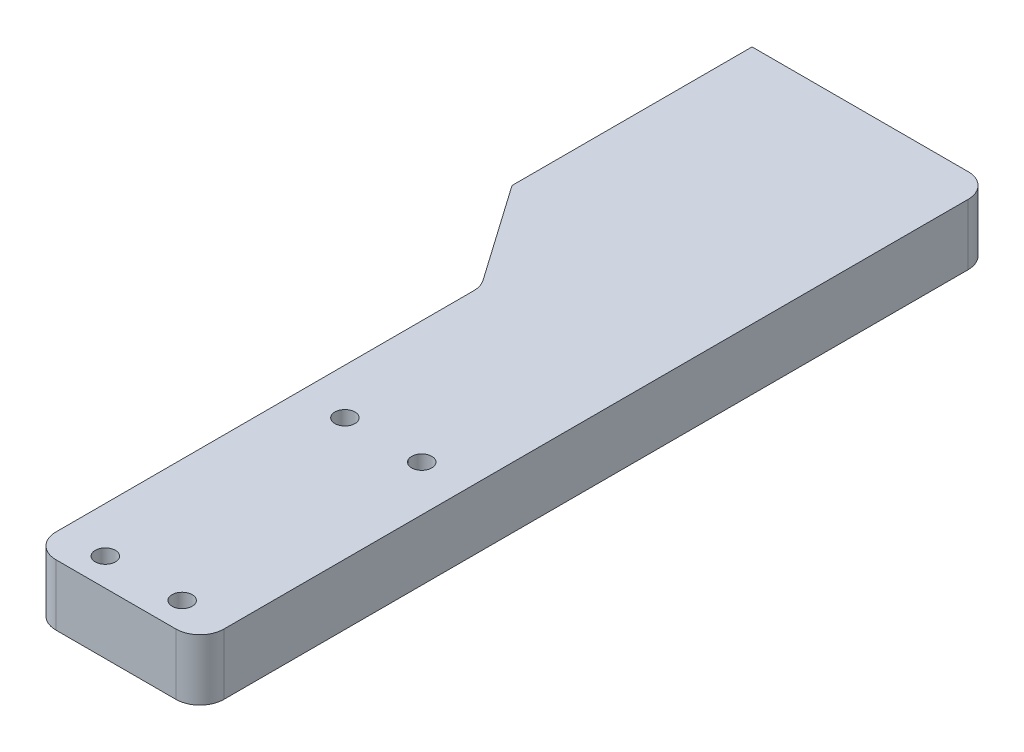
SolidWorks part; units mm, degrees
note: The reader was unsure of these and kept them because the rebuilt part matched: shared geometry of "Sketch26<3>".
ref_plane "Front Plane" through (0, 0, 0) normal (0, 0, 1) x (1, 0, 0)
ref_plane "Top Plane" through (0, 0, 0) normal (0, 1, 0) x (1, 0, 0)
ref_plane "Right Plane" through (0, 0, 0) normal (1, 0, 0) x (0, 0, -1)
sketch "Sketch12" plane through (0, 0, 0) normal (0, 0, 1) x (1, 0, 0)
  line L1 (-25, -6.35) -> (25, -6.35)
  line L2 (-25, -6.35) -> (-25, 6.35)
  line L3 (-25, 6.35) -> (25, 6.35)
  line L4 (25, -6.35) -> (25, 6.35)
  line L5 (0, 6.35) -> (0, -6.35) construction
  line L6 (-25, 0) -> (25, 0) construction
  point P0 (0, 0)
  dimension "D1" = 12.7
  dimension "D2" = 50
extrude "Boss-Extrude1" add sketch "Sketch12" along normal blind 112
sketch "Sketch13" plane through (0, 0, 0) normal (0, 0, -1) x (-1, 0, 0)
  line L0 (-25, 0) -> (25, 0) construction
  line L1 (-25, -6.35) -> (-25, 6.35) construction
  line L2 (25, 6.35) -> (25, -6.35) construction
  point P6 (0, 0)
  point P7 (-17.5, 0)
  point P9 (17.5, 0)
  dimension "D1" = 7.5
  dimension "D2" = 7.5
  dimension "D3" = 35
hole_wizard "M5x0.8 Tapped Hole2" [suppressed] positions "Sketch14" profile "Sketch15" tap size "M5x0.8" standard "ANSI Metric"
sketch "Sketch14" plane through (0, 0, 0) normal (0, 0, -1) x (-1, 0, 0)
  point P0 (-17.5, 0)
  point P3 (0, 0)
  point P6 (17.5, 0)
sketch "Sketch15" plane through (17.5, 0, 0) normal (1, 0, 0) x (0, 1, 0)
  line L0 (0, 0) -> (0, 15.6618)
  line L1 (0, 15.6618) -> (2.1, 14.4)
  line L2 (2.1, 14.4) -> (2.1, 0)
  line L5 (2.1, 0) -> (0, 0)
  line L10 (0, 15.6618) -> (-2.1, 14.4) construction
  line L11 (0, -6.35) -> (0, 107.95) construction
  dimension "Tap Drill Dia." = 4.2
  dimension "Tap Drill Depth" = 14.4
  dimension "Drill Angle" = 118
cosmetic thread "Hole Thread1" [suppressed] parameters "D1"=12, "D2"=5
cosmetic thread "Hole Thread2" [suppressed] parameters "D1"=12, "D2"=5
cosmetic thread "Hole Thread3" [suppressed] parameters "D1"=12, "D2"=5
sketch "Sketch16" plane through (0, 6.35, 0) normal (0, 1, 0) x (1, 0, 0)
  line L0 (15.5, -56.3) -> (-0.5, -56.3) construction
  line L1 (-0.5, -56.3) -> (-0.5, -106.2) construction
  line L2 (-0.5, -106.2) -> (15.5, -106.2) construction
  line L3 (15.5, -106.2) -> (15.5, -56.3) construction
  line L5 (25, -112) -> (25, 0) construction
  line L6 (25, -112) -> (-25, -112) construction
  circle A0 centre (15.5, -56.3) radius 2.75 construction
  circle A1 centre (-0.5, -56.3) radius 2.75 construction
  circle A2 centre (15.5, -106.2) radius 2.75 construction
  circle A3 centre (-0.5, -106.2) radius 2.75 construction
  dimension "D1" = 5.8
  dimension "D4" = 5.5
  dimension "D2" = 49.9
  dimension "D3" = 16
  dimension "D5" = 9.5
hole_wizard "M5x0.8 Tapped Hole3" positions "Sketch17" profile "Sketch18" tap size "M5x0.8" standard "ANSI Metric" end condition through all
sketch "Sketch17" plane through (0, 6.35, 0) normal (0, 1, 0) x (1, 0, 0)
  point P0 (-0.5, -56.3)
  point P3 (15.5, -56.3)
  point P6 (15.5, -106.2)
  point P9 (-0.5, -106.2)
sketch "Sketch18" plane through (-0.5, 6.35, 56.3) normal (1, 0, 0) x (0, 0, 1)
  line L0 (0, 0) -> (0, 12.7)
  line L1 (0, 12.7) -> (2.1, 12.7)
  line L2 (2.1, 12.7) -> (2.1, 0)
  line L5 (2.1, 0) -> (0, 0)
  line L11 (0, -6.35) -> (0, 107.95) construction
  dimension "Thru Tap Drill Dia." = 4.2
  dimension "Thru Tap Drill Depth" = 12.7
cosmetic thread "Hole Thread4" parameters "D2"=5
cosmetic thread "Hole Thread5" parameters "D2"=5
cosmetic thread "Hole Thread6" parameters "D2"=5
cosmetic thread "Hole Thread7" parameters "D2"=5
sketch "Sketch19" plane through (0, 0, 0) normal (0, 0, -1) x (-1, 0, 0)
  line L4 (-25, 6.35) -> (-25, -6.35)
  line L5 (-25, -6.35) -> (25, -6.35)
  line L6 (25, -6.35) -> (25, 6.35)
  line L7 (25, 6.35) -> (-25, 6.35)
  line L8 (-25, 6.35) -> (-25, -6.35)
  line L9 (-25, -6.35) -> (25, -6.35)
  line L10 (25, -6.35) -> (25, 6.35)
  line L11 (25, 6.35) -> (-25, 6.35)
  dimension "D1" = 0
extrude "Boss-Extrude2" add sketch "Sketch19" along normal blind 53
sketch "Sketch20" plane through (-25, 0, 0) normal (-1, 0, 0) x (0, 0, 1)
  line L0 (-53, 0) -> (-3, 0) construction
  line L1 (-53, -6.35) -> (-53, 6.35) construction
  line L2 (-28, 0) -> (-28, 6.35) construction
  line L4 (112, 6.35) -> (-53, 6.35) construction
  circle A0 centre (-19, 0) radius 2.5
  circle A2 centre (-37, 0) radius 2.5
  dimension "D2" = 5
  dimension "D3" = 18
  dimension "D1" = 50
hole_wizard "M5x0.8 Tapped Hole4" positions "Sketch21" profile "Sketch22" tap size "M5x0.8" standard "ANSI Metric"
sketch "Sketch21" plane through (-25, 0, 0) normal (-1, 0, 0) x (0, 0, 1)
  point P0 (-37, 0)
  point P3 (-19, 0)
sketch "Sketch22" plane through (-25, 0, -37) normal (0, 1, 0) x (0, 0, 1)
  line L0 (0, 0) -> (0, 21.2618)
  line L1 (0, 21.2618) -> (2.1, 20)
  line L2 (2.1, 20) -> (2.1, 0)
  line L5 (2.1, 0) -> (0, 0)
  line L10 (0, 21.2618) -> (-2.1, 20) construction
  line L11 (0, -6.35) -> (0, 107.95) construction
  dimension "Tap Drill Dia." = 4.2
  dimension "Tap Drill Depth" = 20
  dimension "Drill Angle" = 118
cosmetic thread "Hole Thread9" parameters "D1"=18, "D2"=5
cosmetic thread "Hole Thread10" parameters "D1"=18, "D2"=5
sketch "Sketch23" [suppressed] plane through (0, -6.35, 0) normal (0, -1, 0) x (1, 0, 0)
  line L0 (-25, 20) -> (25, 20) construction
  line L1 (-25, 112) -> (-25, 0) construction
  line L2 (25, 112) -> (25, 0) construction
  line L3 (-25, 0) -> (25, 0) construction
  line L4 (0, 20) -> (0, 0) construction
  circle A0 centre (-18, 20) radius 2.5
  circle A1 centre (0, 20) radius 2.5
  circle A2 centre (18, 20) radius 2.5
  dimension "D1" = 5
  dimension "D3" = 18
  dimension "D2" = 20
hole_wizard "M5x0.8 Tapped Hole5" [suppressed] positions "Sketch24" profile "Sketch25" tap size "M5x0.8" standard "ANSI Metric"
sketch "Sketch24" plane through (0, -6.35, 0) normal (0, -1, 0) x (-1, 0, 0)
  point P0 (18, -20)
  point P3 (0, -20)
  point P6 (-18, -20)
sketch "Sketch25" plane through (-18, -6.35, 20) normal (1, 0, 0) x (0, 0, -1)
  line L0 (0, 0) -> (0, 12.7)
  line L1 (0, 12.7) -> (2.1, 12.7)
  line L2 (2.1, 12.7) -> (2.1, 0)
  line L5 (2.1, 0) -> (0, 0)
  line L11 (0, -6.35) -> (0, 107.95) construction
  dimension "Thru Tap Drill Dia." = 4.2
  dimension "Thru Tap Drill Depth" = 12.7
cosmetic thread "Hole Thread11" [suppressed] parameters "D2"=5
cosmetic thread "Hole Thread12" [suppressed] parameters "D2"=5
cosmetic thread "Hole Thread13" [suppressed] parameters "D2"=5
sketch "Sketch26" plane through (0, -6.35, 0) normal (0, -1, 0) x (1, 0, 0)
  line L0 (-10, 112) -> (-10, 18.4222)
  line L1 (-25, 112) -> (25, 112) construction
  line L2 (-10, 18.4222) -> (-25, -3)
  line L3 (-25, 112) -> (-25, -53) construction
  line L4 (-25, -3) -> (-25, 112)
  line L5 (-25, 112) -> (-10, 112)
  line L6 (25, -53) -> (-25, -53) construction
  line L7 (25, 112) -> (25, -53) construction
  line L8 (17, -45) -> (-1, -45)
  line L9 (17, -45) -> (17, 48.3)
  line L10 (17, 48.3) -> (-1, 48.3)
  line L11 (-1, -45) -> (-1, 48.3)
  line L12 (8, 48.3) -> (8, -45) construction
  line L13 (17, 1.65) -> (-1, 1.65) construction
  line L15 (17, 98.2) -> (-2, 98.2)
  line L16 (17, 98.2) -> (17, 64.3)
  line L17 (17, 64.3) -> (-2, 64.3)
  line L18 (-2, 98.2) -> (-2, 64.3)
  line L19 (7.5, 64.3) -> (7.5, 98.2) construction
  line L20 (17, 81.25) -> (-2, 81.25) construction
  circle A0 centre (15.5, 56.3) radius 2.1 construction
  circle A1 centre (15.5, 106.2) radius 2.1 construction
  point P139 (8, 1.65)
  point P266 (7.5, 81.25)
  line M9 (-25, 112) -> (-25, -53)
  line M12 (25, 112) -> (-25, 112)
  dimension "D8" = 8
  dimension "D9" = 8
  dimension "D7" = 8
  dimension "D1" = 50
  dimension "D2" = 35
  dimension "D3" = 15
  dimension "D4" = 8
  dimension "D5" = 18
  dimension "D6" = 8
  dimension "D10" = 8
extrude "Cut-Extrude1" cut sketch "Sketch26" against normal through all contours L2 L0 M12 M9
extrude "Cut-Extrude2" cut sketch "Sketch26<3>" against normal blind 9.7 contours L15 L18 L17 L16 | L11 L8 L9 L10
sketch "Sketch26<3>" plane through (0, -6.35, 0) normal (0, -1, 0) x (1, 0, 0) same geometry as "Sketch26"
fillet "Fillet1" radius 5 12 edges at (25, 0, -53) (-10, 0, 18.4222) (25, 0, 112) (-10, 0, 112) (-2, -1.5, 98.2) (17, -1.5, 98.2) (17, -1.5, 64.3) (-2, -1.5, 64.3) (-1, -1.5, -45) (17, -1.5, -45) (-1, -1.5, 48.3) (17, -1.5, 48.3)
